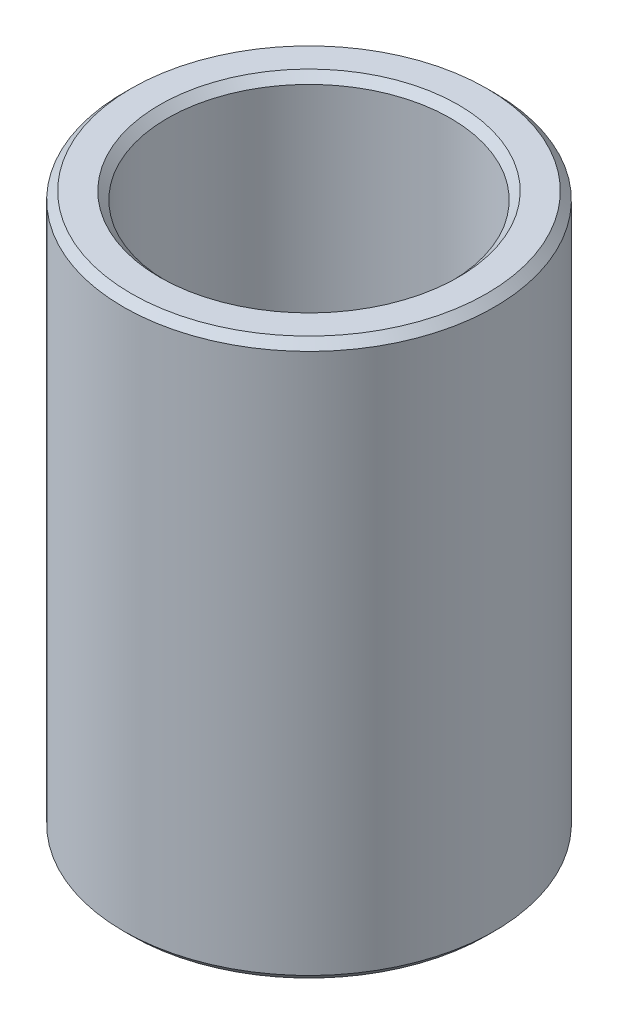
SolidWorks part; units mm, degrees
ref_plane "Front Plane" through (0, 0, 0) normal (0, 0, 1) x (1, 0, 0)
ref_plane "Top Plane" through (0, 0, 0) normal (0, 1, 0) x (1, 0, 0)
ref_plane "Right Plane" through (0, 0, 0) normal (1, 0, 0) x (0, 0, -1)
sketch "Sketch1" plane through (0, 0, 0) normal (0, 1, 0) x (1, 0, 0)
  circle A0 centre (0, 0) radius 40
  dimension "SLEEVE_OD" = 80
extrude "Boss-Extrude1" add sketch "Sketch1" along normal blind 119.8809
sketch "Sketch2" plane through (0, 0, 0) normal (0, 1, 0) x (1, 0, 0)
  circle A0 centre (0, 0) radius 30.5291
  dimension "BORE_D" = 61.0582
extrude "Cut-Extrude1" cut sketch "Sketch2" along normal through all
chamfer "Chamfer1" distance 1.6761 angle 45 4 edges at (0, 119.8809, 30.5291) (0, 0, 30.5291) (0, 0, 40) (0, 119.8809, 40)
